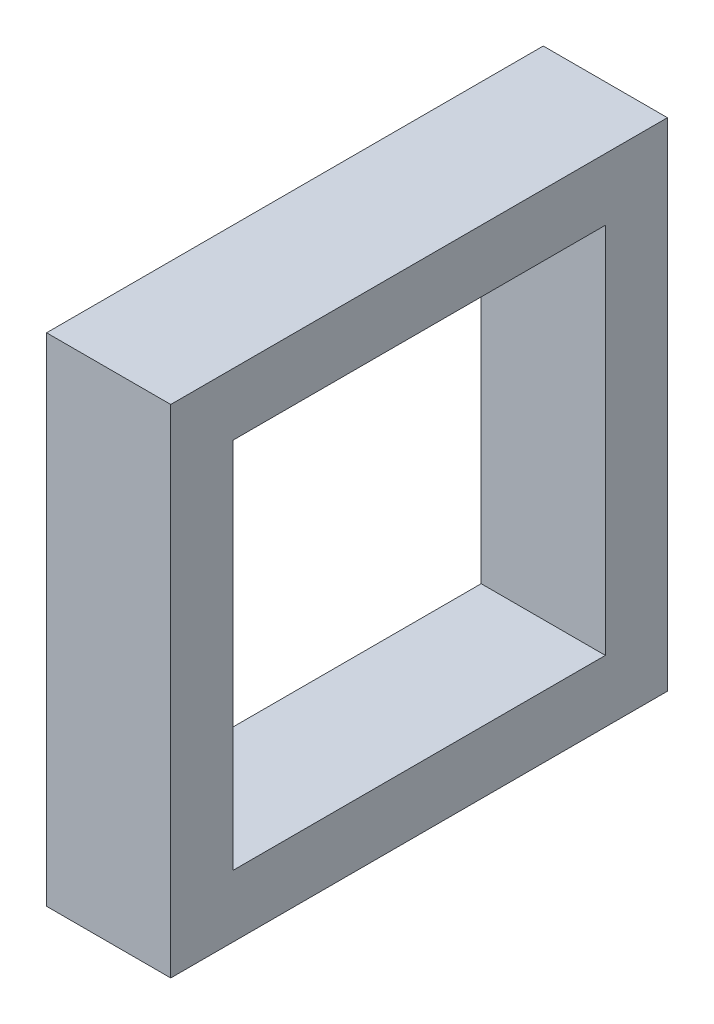
SolidWorks part; units mm, degrees
ref_plane "前视基准面" through (0, 0, 0) normal (0, 0, 1) x (1, 0, 0)
ref_plane "上视基准面" through (0, 0, 0) normal (0, 1, 0) x (1, 0, 0)
ref_plane "右视基准面" through (0, 0, 0) normal (1, 0, 0) x (0, 0, -1)
sketch "草图1" plane through (0, 0, 0) normal (1, 0, 0) x (0, 0, -1)
  line L1 (-2, -2) -> (2, -2)
  line L2 (-2, -2) -> (-2, 2)
  line L3 (-2, 2) -> (2, 2)
  line L4 (2, -2) -> (2, 2)
  line L5 (-2, -2) -> (2, 2) construction
  line L6 (-2, 2) -> (2, -2) construction
  line L7 (1.5, -1.5) -> (-1.5, -1.5)
  line L8 (1.5, -1.5) -> (1.5, 1.5)
  line L9 (1.5, 1.5) -> (-1.5, 1.5)
  line L10 (-1.5, -1.5) -> (-1.5, 1.5)
  line L11 (1.5, -1.5) -> (-1.5, 1.5) construction
  line L12 (1.5, 1.5) -> (-1.5, -1.5) construction
  point P0 (0, 0)
  point P6 (0, 0)
  dimension "D1" = 4
  dimension "D2" = 4
  dimension "D3" = 3
extrude "凸台-拉伸1" add sketch "草图1" along normal blind 1
ref_axis "基准轴1" through (1.05, 0, 0) along (-1, 0, 0)
